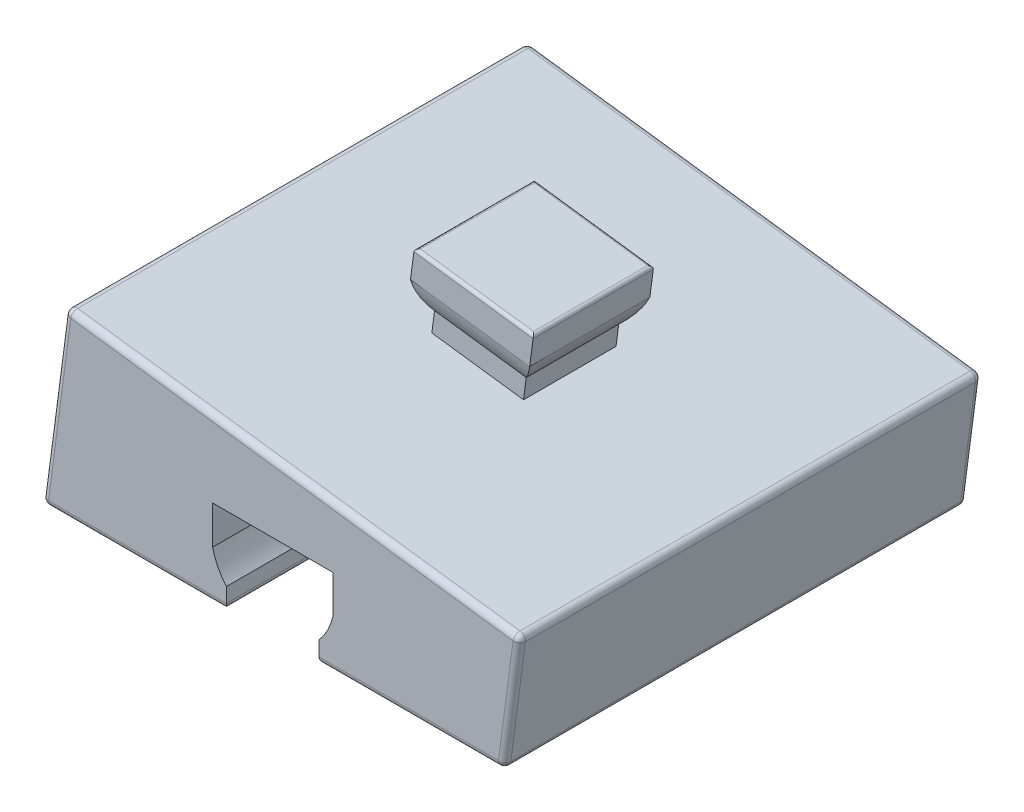
SolidWorks part; units mm, degrees
ref_plane "前视基准面" through (0, 0, 0) normal (0, 0, 1) x (1, 0, 0)
ref_plane "上视基准面" through (0, 0, 0) normal (0, 1, 0) x (1, 0, 0)
ref_plane "右视基准面" through (0, 0, 0) normal (1, 0, 0) x (0, 0, -1)
sketch "草图1" plane through (0, 0, 0) normal (0, 0, 1) x (1, 0, 0)
  line L0 (-7.5, 0) -> (-1.5, 0)
  line L1 (7.5, 0) -> (8.0221, 3.9658)
  line L2 (-7.5, 0) -> (-6.7223, 5.9069)
  line L3 (8.0221, 3.9658) -> (-6.7223, 5.9069)
  line L4 (-1.95, 2.8) -> (1.95, 2.8)
  line L5 (-1.95, 2.8) -> (-1.95, 1.5556)
  line L6 (1.95, 2.8) -> (1.95, 1.5556)
  line L7 (1.5, 0) -> (7.5, 0)
  line L9 (-1.5, 0) -> (-1.5, 0.6771)
  line L11 (1.5, 0) -> (1.5, 0.6771)
  arc A0 (1.5, 0.6771) -> (1.95, 1.5556) centre (0, 2) ccw
  arc A2 (-1.95, 1.5556) -> (-1.5, 0.6771) centre (0, 2) ccw
extrude "凸台-拉伸1" add sketch "草图1" along normal blind 7.5 and the other way blind 7.5
sketch "草图2" plane through (0, 0, 0) normal (0, 0, 1) x (1, 0, 0)
  line L0 (-0.8373, 5.1321) -> (2.1371, 4.7406)
  line L2 (8.0221, 3.9658) -> (-6.7223, 5.9069) construction
  line L3 (2.1371, 4.7406) -> (2.2676, 5.732)
  line L4 (2.2676, 5.732) -> (-0.7068, 6.1236)
  line L5 (-0.7068, 6.1236) -> (-0.8373, 5.1321)
extrude "凸台-拉伸2" add sketch "草图2" along normal blind 1.5 and the other way blind 1.5
sketch "草图3" plane through (0, 0, 0) normal (0, 0, 1) x (1, 0, 0)
  line L0 (0.7383, 5.6077) -> (1.0056, 7.638) construction
  line L1 (-0.9571, 7.6695) -> (-1.0804, 6.7332)
  line L3 (2.9095, 7.1604) -> (2.7862, 6.2241)
  line L5 (-0.9571, 7.6695) -> (2.9095, 7.1604)
  line L6 (2.1371, 4.7406) -> (2.2676, 5.732) construction
  line L7 (2.2254, 5.4119) -> (-0.7489, 5.8035)
  arc A0 (2.2254, 5.4119) -> (2.7862, 6.2241) centre (0.9109, 6.9192) ccw
  arc A1 (-0.7489, 5.8035) -> (-1.0804, 6.7332) centre (0.9109, 6.9192) cw
  point P5 (0.9762, 7.415)
extrude "凸台-拉伸3" add sketch "草图3" along normal blind 2 and the other way blind 2
sketch "草图4" plane through (1.9333, -0.2545, 0) normal (0.9914, -0.1305, 0) x (0, 0, -1)
  line L0 (1.95, 7.4789) -> (2, 7.4789)
  line L3 (-1.95, 7.4789) -> (-1.95, 6.5345)
  line L6 (1.95, 7.4789) -> (1.95, 6.5345)
  line L8 (1.5, 5.6561) -> (2, 5.6561)
  line L9 (-2, 7.4789) -> (-1.95, 7.4789)
  line L10 (-2, 7.4789) -> (-2, 5.6561)
  line L11 (-2, 5.6561) -> (-1.5, 5.6561)
  line L12 (2, 7.4789) -> (2, 5.6561)
  arc A0 (1.5, 5.6561) -> (1.95, 6.5345) centre (0, 6.9789) ccw
  arc A2 (-1.95, 6.5345) -> (-1.5, 5.6561) centre (0, 6.9789) ccw
extrude "切除-拉伸1" cut sketch "草图4" against normal through all
fillet "圆角1" radius 0.2 16 edges at (-4.5, 0, -7.5) (-7.5, 0, 0) (-4.5, 0, 7.5) (-1.5, 0, 0) (4.5, 0, -7.5) (1.5, 0, 0) (4.5, 0, 7.5) (7.5, 0, 0) (0.6499, 4.9364, -7.5) (-6.7223, 5.9069, 0) (8.0221, 3.9658, 0) (0.6499, 4.9364, 7.5) (-7.1112, 2.9535, -7.5) (-7.1112, 2.9535, 7.5) (7.7611, 1.9829, -7.5) (7.7611, 1.9829, 7.5)
fillet "圆角2" radius 0.1 4 edges at (2.9095, 7.1604, 0) (0.9762, 7.415, 1.95) (-0.9571, 7.6695, 0) (0.9762, 7.415, -1.95)
